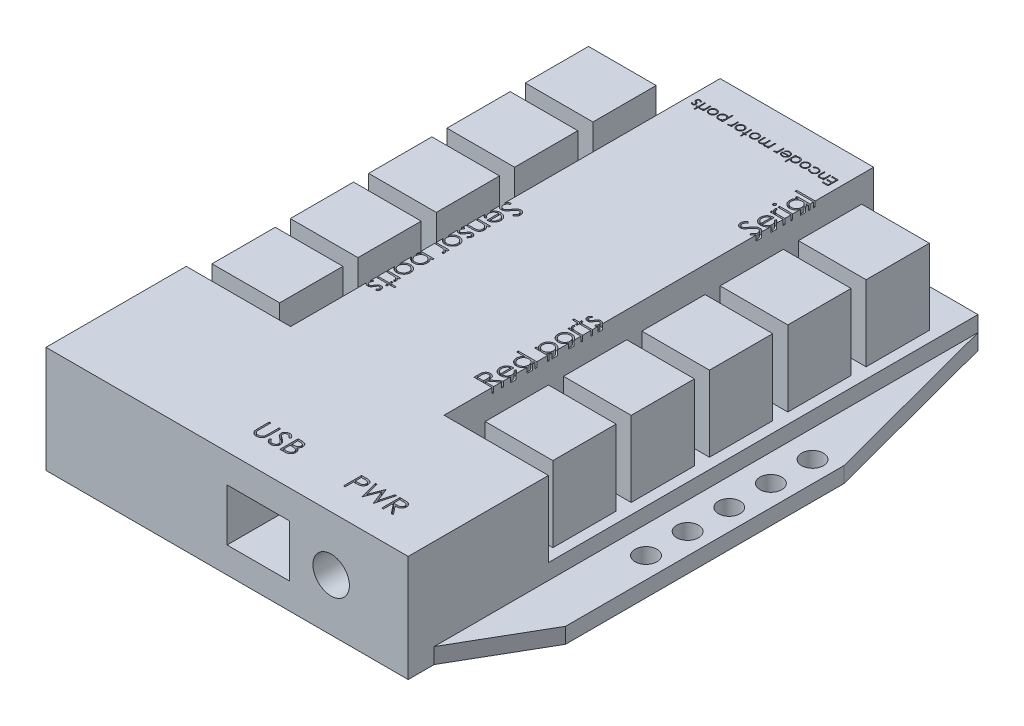
SolidWorks part; units mm, degrees
ref_plane "Front Plane" through (0, 0, 0) normal (0, 0, 1) x (1, 0, 0)
ref_plane "Top Plane" through (0, 0, 0) normal (0, 1, 0) x (1, 0, 0)
ref_plane "Right Plane" through (0, 0, 0) normal (1, 0, 0) x (0, 0, -1)
sketch "Sketch1" plane through (0, 0, 0) normal (0, 1, 0) x (1, 0, 0)
  line L1 (-34.8, 0) -> (34.8, 0)
  line L2 (-34.8, 0) -> (-34.8, 109.5)
  line L3 (-34.8, 109.5) -> (34.8, 109.5)
  line L4 (34.8, 0) -> (34.8, 109.5)
  point P6 (0, 0)
  dimension "D1" = 69.6
  dimension "D2" = 109.5
extrude "Boss-Extrude1" add sketch "Sketch1" along normal blind 20.5
sketch "Sketch2" plane through (0, 0, 0) normal (0, 1, 0) x (1, 0, 0)
  line L0 (-34.8, 109.5) -> (-44.05, 74.5)
  line L1 (-34.8, 109.5) -> (-34.8, 0) construction
  line L2 (-44.05, 74.5) -> (-44.05, 21)
  line L3 (-44.05, 21) -> (-34.8, 5)
  line L4 (-34.8, 5) -> (-34.8, 109.5)
  dimension "D3" = 16
  dimension "D1" = 35
  dimension "D4" = 5
  dimension "D2" = 44.05
extrude "Boss-Extrude2" add sketch "Sketch2" along normal blind 3
sketch "Sketch3" plane through (0, 3, 0) normal (0, 1, 0) x (1, 0, 0)
  line L0 (0, -1000) -> (0, 49000) construction
  line L1 (-40, 13.9946) -> (-40, 89.8243) construction
  line L2 (-34.8, 109.5) -> (-44.05, 74.5) construction
  line L3 (-44.05, 21) -> (-34.8, 5) construction
  line L4 (34.8, 109.5) -> (-34.8, 109.5) construction
  line L5 (-34.8, 0) -> (34.8, 0) construction
  circle A5 centre (-40, 72.5) radius 2.1
  circle A6 centre (-40, 64.5) radius 2.1
  circle A7 centre (-40, 56.5) radius 2.1
  circle A8 centre (-40, 48.5) radius 2.1
  circle A9 centre (-40, 40.5) radius 2.1
  dimension "D1" = 4.2
  dimension "D2" = 16
  dimension "D3" = 16
  dimension "D4" = 8
  dimension "D5" = 8
  dimension "D8" = 40
  dimension "D6" = 39.1
  dimension "D7" = 42.6
extrude "Cut-Extrude1" cut sketch "Sketch3" against normal through all
mirror "Mirror1" about plane through (0, 0, 0) normal (1, 0, 0) of "Cut-Extrude1", "Boss-Extrude2"
sketch "Sketch4" plane through (0, 0, 0) normal (0, 0, 1) x (1, 0, 0)
  line L0 (-34.8, 0) -> (34.8, 0) construction
  line L1 (0, 15) -> (12, 15)
  line L2 (0, 15) -> (0, 5)
  line L3 (0, 5) -> (12, 5)
  line L4 (12, 15) -> (12, 5)
  circle A0 centre (20, 10) radius 3.5
  point P14 (12, 10)
  dimension "D3" = 7
  dimension "D5" = 8
  dimension "D1" = 12
  dimension "D2" = 10
  dimension "D4" = 5
extrude "Cut-Extrude2" cut sketch "Sketch4" against normal blind 10
sketch "Sketch6" plane through (0, 20.5, 0) normal (0, 1, 0) x (1, 0, 0)
  line L1 (-32.75, 102.2) -> (-19.75, 102.2)
  line L2 (-32.75, 102.2) -> (-32.75, 90.05)
  line L3 (-32.75, 90.05) -> (-19.75, 90.05)
  line L4 (-19.75, 102.2) -> (-19.75, 90.05)
  line L5 (-44.05, 74.5) -> (-44.05, 21) construction
  line L10 (34.8, 109.5) -> (-34.8, 109.5) construction
  line L12 (-32.75, 87.15) -> (-14.75, 87.15)
  line L13 (-32.75, 87.15) -> (-32.75, 105.1)
  line L14 (-32.75, 105.1) -> (-14.75, 105.1)
  line L15 (-14.75, 87.15) -> (-14.75, 105.1)
  line L16 (-32.75, 87.15) -> (-32.75, 75)
  line L17 (-32.75, 87.15) -> (-19.75, 87.15)
  line L18 (-19.75, 87.15) -> (-19.75, 75)
  line L19 (-32.75, 75) -> (-19.75, 75)
  line L20 (-32.75, 72.1) -> (-32.75, 90.05)
  line L21 (-32.75, 72.1) -> (-14.75, 72.1)
  line L22 (-14.75, 72.1) -> (-14.75, 90.05)
  line L23 (-32.75, 90.05) -> (-14.75, 90.05)
  line L24 (-32.75, 72.1) -> (-32.75, 59.95)
  line L25 (-32.75, 72.1) -> (-19.75, 72.1)
  line L26 (-19.75, 72.1) -> (-19.75, 59.95)
  line L27 (-32.75, 59.95) -> (-19.75, 59.95)
  line L28 (-32.75, 57.05) -> (-32.75, 75)
  line L29 (-32.75, 57.05) -> (-14.75, 57.05)
  line L30 (-14.75, 57.05) -> (-14.75, 75)
  line L31 (-32.75, 75) -> (-14.75, 75)
  line L32 (-32.75, 57.05) -> (-32.75, 44.9)
  line L33 (-32.75, 57.05) -> (-19.75, 57.05)
  line L34 (-19.75, 57.05) -> (-19.75, 44.9)
  line L35 (-32.75, 44.9) -> (-19.75, 44.9)
  line L36 (-32.75, 42) -> (-32.75, 59.95)
  line L37 (-32.75, 42) -> (-14.75, 42)
  line L38 (-14.75, 42) -> (-14.75, 59.95)
  line L39 (-32.75, 59.95) -> (-14.75, 59.95)
  line L40 (-32.75, 42) -> (-32.75, 29.85)
  line L41 (-32.75, 42) -> (-19.75, 42)
  line L42 (-19.75, 42) -> (-19.75, 29.85)
  line L43 (-32.75, 29.85) -> (-19.75, 29.85)
  line L44 (-32.75, 26.95) -> (-32.75, 44.9)
  line L45 (-32.75, 26.95) -> (-14.75, 26.95)
  line L46 (-14.75, 26.95) -> (-14.75, 44.9)
  line L47 (-32.75, 44.9) -> (-14.75, 44.9)
  line L48 (-32.75, 109.5) -> (-14.75, 109.5)
  line L49 (-32.75, 109.5) -> (-32.75, 105.1)
  line L50 (-32.75, 105.1) -> (-14.75, 105.1)
  line L51 (-14.75, 109.5) -> (-14.75, 105.1)
  line L52 (-34.8, 5) -> (-34.8, 109.5) construction
  line L53 (-32.75, 109.5) -> (-34.8, 109.5)
  line L54 (-32.75, 109.5) -> (-32.75, 26.95)
  line L55 (-32.75, 26.95) -> (-34.8, 26.95)
  line L56 (-34.8, 109.5) -> (-34.8, 26.95)
  line M13 (-34.8, 109.5) -> (-34.8, 0)
  line M16 (34.8, 109.5) -> (-34.8, 109.5)
  dimension "D1" = 13
  dimension "D2" = 12.15
  dimension "D3" = 7.3
  dimension "D4" = 2.9
  dimension "D5" = 2.9
  dimension "D6" = 5
  dimension "D8" = 11.3
  dimension "D9" = 72.35
  dimension "D7" = 5
extrude "Cut-Extrude4" cut sketch "Sketch6" against normal offset from surface (14.5 mm away) 3 contours L4 L23 L15 L14 L1 M13 | L23 L3 L12 L15 M13 | L18 L31 L22 L12 | L31 L19 L21 L22 M13 | L26 L39 L30 L21 | L39 L27 L29 L30 M13 | L34 L47 L38 L29 | L47 L35 L37 L38 M13 | L45 L46 L37 L42 L43 M13 | L51 L49 L14 M16 | L55 L44 L40 L36 L32 L28 L24 L20 L16 L13 L2 L49 M16 M13 region at (-32.5154, 20.5, -103.65) region at (-33.775, 20.5, -68.225) region at (-23.75, 20.5, -88.6) region at (-23.75, 20.5, -107.3) region at (-17.25, 20.5, -81.075) region at (-23.75, 20.5, -73.55) region at (-17.25, 20.5, -66.025) region at (-23.75, 20.5, -58.5) region at (-32.5154, 20.5, -28.4) region at (-17.25, 20.5, -50.975) region at (-23.75, 20.5, -43.45) up to face at (-40, 3, -70.4)
mirror "Mirror2" about plane through (0, 0, 0) normal (1, 0, 0) of "Cut-Extrude4"
sketch "Sketch5" plane through (0, 20.5, 0) normal (0, 1, 0) x (1, 0, 0)
  line L0 (-34.8, 104) -> (34.8, 104) construction
  line L1 (-34.8, 26.95) -> (-34.8, 0) construction
  line L2 (34.8, 0) -> (34.8, 26.95) construction
  line L3 (14.75, 109.5) -> (-14.75, 109.5) construction
  line L4 (-34.8, 5.5) -> (34.8, 5.5) construction
  line L5 (-34.8, 0) -> (34.8, 0) construction
  line L6 (-14.8, 5.5) -> (-14.8, 104) construction
  line L7 (14.8, 104) -> (14.8, 5.5) construction
  text T0 "Encoder motor ports" font "Century Gothic" height 2
  text T1 "USB       PWR      "
  text T2 "Sensor ports"
  text T3 "Red ports                     Serial    "
  dimension "D1" = 5.5
  dimension "D2" = 5.5
  dimension "D3" = 20
  dimension "D4" = 20
extrude "Cut-Extrude3" cut sketch "Sketch5" against normal blind 1
equation "\"width\"= 24"
equation "\"thk\"= 3"
equation "\"holesize\"= 4.2"
equation "\"holedistance\"= ( 20 + 12 ) / 2"
equation "\"threaded_hole\"= 3.9"
equation "\"fillet_radius\"= 2"
equation "\"ground_clearance\"= 25"
equation "\"tire_thk\"= 3"
equation "\"innerwheel_diam\" = \"wheel_diam\"-2*\"tire_thk\""
equation "\"innerwheel_thk\"= 8"
equation "\"wheel_diam\"= 2*(\"width\"/2+\"ground_clearance\")"
equation "\"D1@Sketch3\"=\"holesize\""
equation "\"D2@Sketch3\"=\"holedistance\""
equation "\"D3@Sketch3\"=\"holedistance\""
equation "\"D4@Sketch3\"=\"D2@Sketch3\"/2"
equation "\"D5@Sketch3\"=\"D3@Sketch3\"/2"
equation "\"D2@Sketch5\"=\"D1@Sketch5\""
equation "\"D4@Sketch5\"=\"D3@Sketch5\""
equation "\"D8@Sketch3\"=80/2"
equation "\"D2@Sketch2\"=88.1/2"
equation "\"coloursensor_holesize\"= 2.65"
equation "\"hole_to_edge\" = 4"
equation "\"D5@Sketch6\"=\"D4@Sketch6\""
